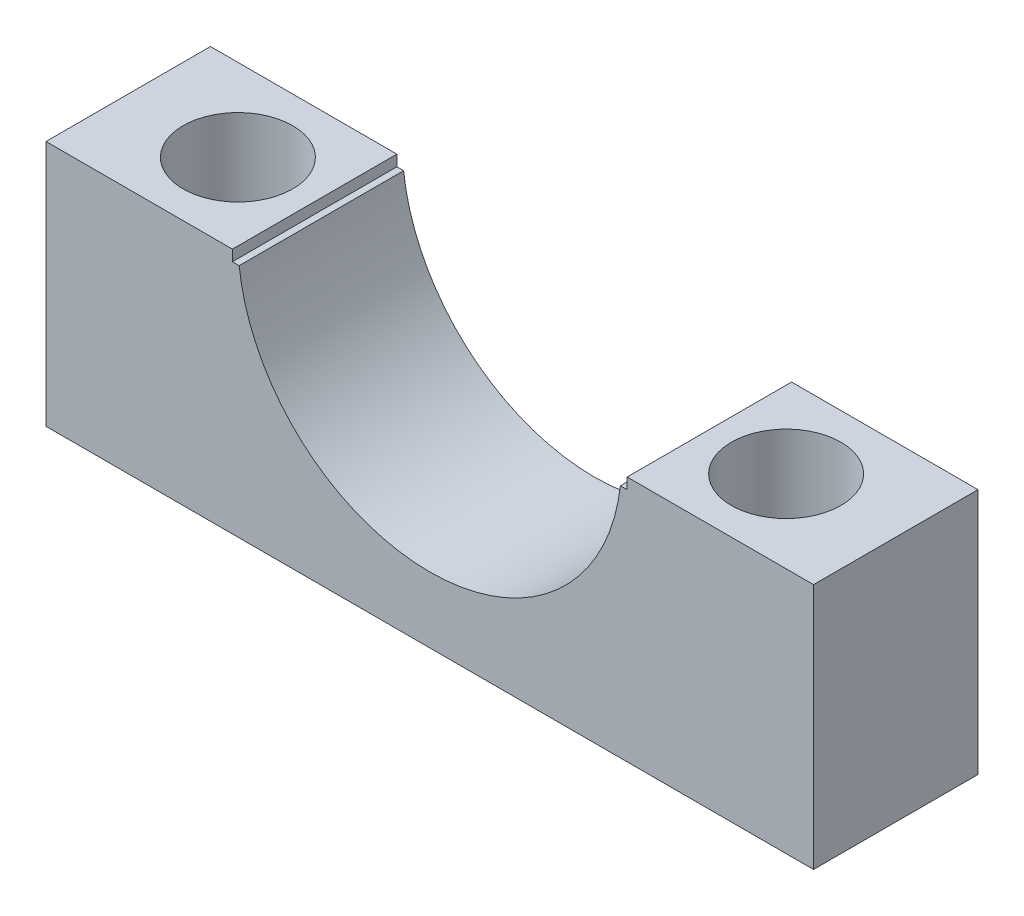
SolidWorks part; units mm, degrees
ref_plane "Front Plane" through (0, 0, 0) normal (0, 0, 1) x (1, 0, 0)
ref_plane "Top Plane" through (0, 0, 0) normal (0, 1, 0) x (1, 0, 0)
ref_plane "Right Plane" through (0, 0, 0) normal (1, 0, 0) x (0, 0, -1)
sketch "Sketch1" plane through (0, 0, 0) normal (0, 0, 1) x (1, 0, 0)
  line L0 (0, 0) -> (0, 25.6344) construction
  line L1 (35, 0) -> (-35, 0)
  line L2 (-35, 0) -> (-35, 22.5)
  line L3 (-35, 22.5) -> (-18, 22.5)
  line L4 (35, 22.5) -> (18, 22.5)
  line L5 (35, 0) -> (35, 22.5)
  line L6 (18, 22.5) -> (18, 21.5)
  line L7 (18, 21.5) -> (17.3853, 21.5)
  line L8 (-18, 21.5) -> (-17.3853, 21.5)
  line L9 (-18, 22.5) -> (-18, 21.5)
  arc A0 (-17.3853, 21.5) -> (17.3853, 21.5) centre (0, 23.5) ccw
  dimension "D1" = 17.5
  dimension "D2" = 35
  dimension "D3" = 22.5
  dimension "D4" = 1
  dimension "D5" = 90
  dimension "D6" = 17
  dimension "D7" = 23.5
extrude "Boss-Extrude1" add sketch "Sketch1" along normal blind 15
sketch "Sketch2" plane through (0, 0, 0) normal (0, 1, 0) x (1, 0, 0)
  line L0 (-35, -15) -> (-35, 0) construction
  line L2 (-18, -15) -> (-35, -15) construction
  line L3 (0, 0) -> (0, -21.8102) construction
  circle A0 centre (-25, -7.5) radius 5
  circle A1 centre (25, -7.5) radius 5
  point P8 (-35, -7.5)
  dimension "D1" = 10
  dimension "D2" = 25
  dimension "D3" = 7.5
extrude "Cut-Extrude1" cut sketch "Sketch2" along normal through all
sketch "Sketch4" plane through (0, 22.5, 0) normal (0, 1, 0) x (-1, 0, 0)
  line L0 (-21, 30.8506) -> (-21, 32.3506)
  line L2 (-21.9089, 32.3506) -> (-21, 32.3506)
  line L3 (0, 31.8506) -> (0, 48.8506)
  line L4 (-21.9089, 49.3506) -> (-21, 49.3506)
  line L6 (18, 15) -> (-18, 15) construction
  line L8 (-21, 49.3506) -> (-21, 50.8506)
  line L10 (-21, 30.8506) -> (0, 30.8506)
  line L11 (0, 30.8506) -> (0, 31.8506)
  line L12 (-21, 50.8506) -> (0, 50.8506)
  line L13 (0, 50.8506) -> (0, 48.8506)
  line L14 (0, 15) -> (0, 0) construction
  arc A0 (-21.9089, 32.3506) -> (-21.9089, 49.3506) centre (0, 40.8506) cw
  point P0 (31.5681, 26.9336)
  point P5 (0, 40.3506)
  point P6 (-23.5, 40.8506)
  point P16 (0, 0)
  point P17 (0, 0)
  point P20 (0, 0)
  point P21 (0, 0)
  point P22 (0, 0)
  point P23 (0, 0)
  point P27 (0, 0)
  point P28 (0, 0)
  point P29 (0, 0)
  point P30 (0, 0)
  point P31 (0, 0)
  point P32 (0, 0)
  point P33 (0, 7.5)
  dimension "D2" = 23.5
  dimension "D1" = 17
  dimension "D3" = 21
  dimension "D4" = 1.5
  dimension "D5" = 1.5
  dimension "D6" = 0.9089
